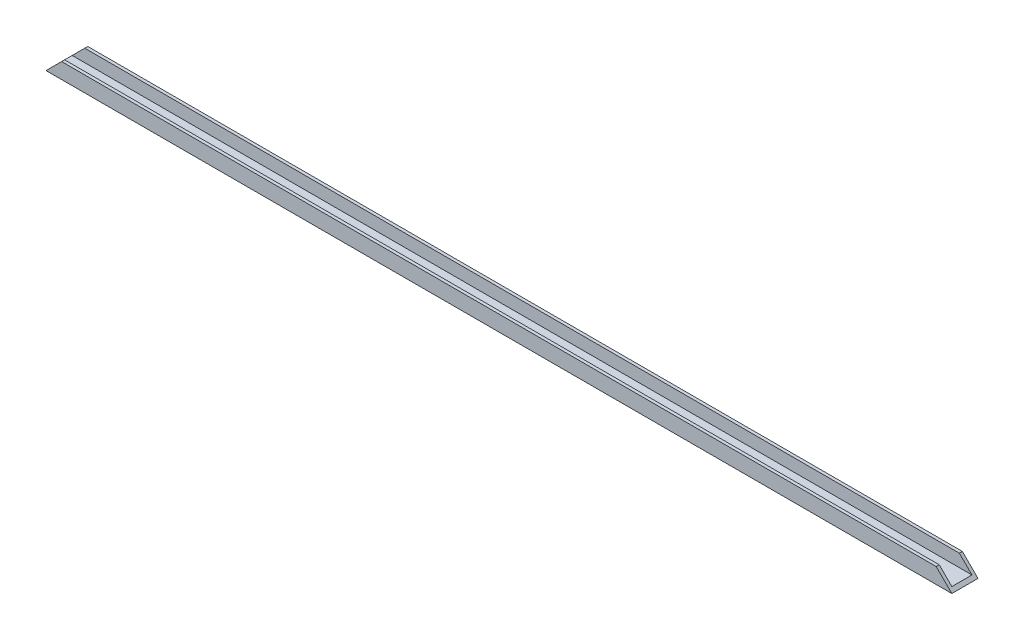
SolidWorks part; units mm, degrees
ref_plane "Front Plane" through (0, 0, 0) normal (0, 0, 1) x (1, 0, 0)
ref_plane "Top Plane" through (0, 0, 0) normal (0, 1, 0) x (1, 0, 0)
ref_plane "Right Plane" through (0, 0, 0) normal (1, 0, 0) x (0, 0, -1)
sketch "Sketch1" plane through (0, 0, 0) normal (1, 0, 0) x (0, 0, -1)
  line L0 (-4, 5) -> (-4, 0)
  line L1 (-4, 0) -> (4, 0)
  line L2 (4, 0) -> (4, 5)
  line L3 (-5.2, 5) -> (-5.2, -1.2)
  line L4 (-5.2, -1.2) -> (5.2, -1.2)
  line L5 (5.2, -1.2) -> (5.2, 5)
  line L6 (-5.2, 5) -> (-4, 5)
  line L7 (4, 5) -> (5.2, 5)
  point P2 (0, 0)
  point P8 (0, -1.2)
  dimension "D1" = 5
  dimension "D2" = 5
  dimension "D3" = 8
  dimension "D4" = 1.2
  dimension "D5" = 1.2
  dimension "D6" = 1.2
extrude "Boss-Extrude1" add sketch "Sketch1" along normal mid plane 360
sketch "Sketch3" plane through (0, 0, 5.2) normal (0, 0, 1) x (1, 0, 0)
  line L0 (-180, 5) -> (-180, -1.2)
  line L1 (-180, -1.2) -> (-173.8, 5)
  line L2 (180, 5) -> (-180, 5) construction
  line L3 (-173.8, 5) -> (-180, 5)
  line L4 (0, 32.8147) -> (0, -57.253) construction
  line L5 (180, 5) -> (180, -1.2)
  line L6 (173.8, 5) -> (180, 5)
  line L7 (180, -1.2) -> (173.8, 5)
  dimension "D1" = 45
extrude "Cut-Extrude1" cut sketch "Sketch3" against normal through all
